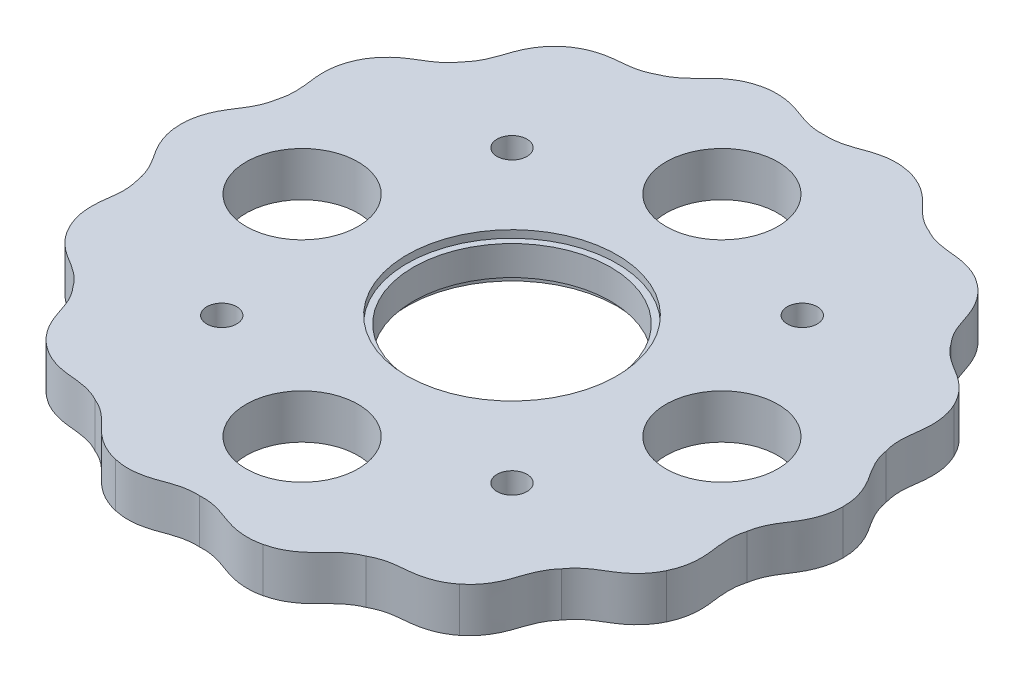
SolidWorks part; units mm, degrees
ref_plane "Front Plane" through (0, 0, 0) normal (0, 0, 1) x (1, 0, 0)
ref_plane "Top Plane" through (0, 0, 0) normal (0, 1, 0) x (1, 0, 0)
ref_plane "Right Plane" through (0, 0, 0) normal (1, 0, 0) x (0, 0, -1)
sketch "Sketch1" plane through (0, 0, 0) normal (0, 1, 0) x (1, 0, 0)
  line L0 (0, 0) -> (37.5, 0) construction
  line L1 (0, 0) -> (37.4807, 1.2019) construction
  line L2 (0, 0) -> (37.423, 2.4026) construction
  line L3 (0, 0) -> (37.3267, 3.6009) construction
  line L4 (0, 0) -> (37.1921, 4.7954) construction
  line L5 (0, 0) -> (37.0193, 5.985) construction
  line L6 (0, 0) -> (36.8085, 7.1684) construction
  line L7 (0, 0) -> (36.5598, 8.3445) construction
  line L8 (0, 0) -> (36.2736, 9.512) construction
  line L9 (0, 0) -> (35.95, 10.6698) construction
  line L10 (0, 0) -> (35.5896, 11.8166) construction
  line L11 (0, 0) -> (35.1926, 12.9512) construction
  line L12 (0, 0) -> (34.7594, 14.0725) construction
  line L13 (0, 0) -> (34.2905, 15.1794) construction
  line L14 (0, 0) -> (33.7863, 16.2706) construction
  line L15 (37.5, 0) -> (38.5, 0) construction
  line L16 (37.4807, 1.2019) -> (38.3521, 1.6927) construction
  line L17 (37.423, 2.4026) -> (37.9413, 3.2578) construction
  line L18 (37.3267, 3.6009) -> (37.3588, 4.6003) construction
  line L19 (37.1921, 4.7954) -> (36.7296, 5.682) construction
  line L20 (37.0193, 5.985) -> (36.1812, 6.5305) construction
  line L21 (36.8085, 7.1684) -> (35.8105, 7.2325) construction
  line L22 (36.5598, 8.3445) -> (35.5849, 8.122) construction
  line L23 (37, 0.0019) -> (37, 0)
  line L24 (33.3367, 16.052) -> (33.3358, 16.0537)
  line L25 (37, -0.0019) -> (37, 0)
  line L26 (33.3367, -16.052) -> (33.3358, -16.0537)
  line L27 (33.335, -16.0554) -> (33.3358, -16.0537)
  line L28 (23.0706, -28.9266) -> (23.0691, -28.9278)
  line L29 (23.0677, -28.9289) -> (23.0691, -28.9278)
  line L30 (8.2351, -36.0719) -> (8.2333, -36.0723)
  line L31 (8.2315, -36.0727) -> (8.2333, -36.0723)
  line L32 (-8.2315, -36.0727) -> (-8.2333, -36.0723)
  line L33 (-8.2351, -36.0719) -> (-8.2333, -36.0723)
  line L34 (-23.0677, -28.9289) -> (-23.0691, -28.9278)
  line L35 (-23.0706, -28.9266) -> (-23.0691, -28.9278)
  line L36 (-33.335, -16.0554) -> (-33.3358, -16.0537)
  line L37 (-33.3367, -16.052) -> (-33.3358, -16.0537)
  line L38 (-37, -0.0019) -> (-37, 0)
  line L39 (-37, 0.0019) -> (-37, 0)
  line L40 (-33.3367, 16.052) -> (-33.3358, 16.0537)
  line L41 (-33.335, 16.0554) -> (-33.3358, 16.0537)
  line L42 (-23.0706, 28.9266) -> (-23.0691, 28.9278)
  line L43 (-23.0677, 28.9289) -> (-23.0691, 28.9278)
  line L44 (-8.2351, 36.0719) -> (-8.2333, 36.0723)
  line L45 (-8.2315, 36.0727) -> (-8.2333, 36.0723)
  line L46 (8.2315, 36.0727) -> (8.2333, 36.0723)
  line L47 (8.2351, 36.0719) -> (8.2333, 36.0723)
  line L48 (23.0677, 28.9289) -> (23.0691, 28.9278)
  line L49 (23.0706, 28.9266) -> (23.0691, 28.9278)
  line L50 (33.335, 16.0554) -> (33.3358, 16.0537)
  line L51 (35.5, 0.0037) -> (35.5, 0)
  line L52 (31.986, 15.3995) -> (31.9844, 15.4029)
  line L53 (35.5, -0.0037) -> (35.5, 0)
  line L54 (31.986, -15.3995) -> (31.9844, -15.4029)
  line L55 (31.9828, -15.4062) -> (31.9844, -15.4029)
  line L56 (22.1368, -27.7527) -> (22.1339, -27.755)
  line L57 (22.131, -27.7573) -> (22.1339, -27.755)
  line L58 (7.9031, -34.6091) -> (7.8995, -34.6099)
  line L59 (7.8959, -34.6108) -> (7.8995, -34.6099)
  line L60 (-7.8959, -34.6108) -> (-7.8995, -34.6099)
  line L61 (-7.9031, -34.6091) -> (-7.8995, -34.6099)
  line L62 (-22.131, -27.7573) -> (-22.1339, -27.755)
  line L63 (-22.1368, -27.7527) -> (-22.1339, -27.755)
  line L64 (-31.9828, -15.4062) -> (-31.9844, -15.4029)
  line L65 (-31.986, -15.3995) -> (-31.9844, -15.4029)
  line L66 (-35.5, -0.0037) -> (-35.5, 0)
  line L67 (-35.5, 0.0037) -> (-35.5, 0)
  line L68 (-31.986, 15.3995) -> (-31.9844, 15.4029)
  line L69 (-31.9828, 15.4062) -> (-31.9844, 15.4029)
  line L70 (-22.1368, 27.7527) -> (-22.1339, 27.755)
  line L71 (-22.131, 27.7573) -> (-22.1339, 27.755)
  line L72 (-7.9031, 34.6091) -> (-7.8995, 34.6099)
  line L73 (-7.8959, 34.6108) -> (-7.8995, 34.6099)
  line L74 (7.8959, 34.6108) -> (7.8995, 34.6099)
  line L75 (7.9031, 34.6091) -> (7.8995, 34.6099)
  line L76 (22.131, 27.7573) -> (22.1339, 27.755)
  line L77 (22.1368, 27.7527) -> (22.1339, 27.755)
  line L78 (31.9828, 15.4062) -> (31.9844, 15.4029)
  circle A0 centre (0, 0) radius 35 construction
  circle A1 centre (37.5, 0) radius 2.5 construction
  circle A2 centre (0, 0) radius 37.5 construction
  spline S0 degree 3 poles (35.5849, 8.122) (35.6266, 7.5364) (36.0345, 6.7125) (36.7836, 5.6218) (37.4152, 4.5501) (38.2239, 2.702) (38.5014, 1.1074) (38.5, 0) knots 0 0 0 0 0.195516 0.310928 0.453873 0.621058 1 1 1 1
  spline S1 degree 3 poles (35.5849, 8.122) (35.3683, 8.6678) (35.3784, 9.5871) (35.5801, 10.8948) (35.6841, 12.1344) (35.611, 14.1503) (35.169, 15.7074) (34.6873, 16.7045) knots 0 0 0 0 0.195516 0.310928 0.453873 0.621058 1 1 1 1
  spline S2 degree 1 poles (34.1119, 7.7858) (33.3367, 16.052) knots 0 0 1 1 construction
  spline S3 degree 1 poles (34.1119, 7.7858) (37, 0.0019) knots 0 0 1 1 construction
  spline S4 degree 3 poles (33.3367, 16.052) (33.6005, 15.5058) (33.9037, 14.6401) (34.1146, 13.4372) (34.174, 12.5211) (34.1413, 11.5771) (34.0239, 10.6392) (33.8823, 9.6155) (33.9055, 8.625) (34.0243, 8.0514) (34.1119, 7.7858) knots 0.015853 0.015853 0.015853 0.015853 0.26189 0.384908 0.507927 0.630945 0.753963 0.876982 0.938491 1 1 1 1
  spline S5 degree 3 poles (34.1119, 7.7858) (34.1483, 7.5085) (34.2901, 6.9402) (34.6989, 6.0377) (35.2706, 5.1769) (35.7834, 4.3828) (36.2224, 3.5464) (36.5664, 2.6953) (36.8983, 1.52) (37.0008, 0.6085) (37, 0.0019) knots 0.015853 0.015853 0.015853 0.015853 0.077362 0.138872 0.26189 0.384908 0.507927 0.630945 0.753963 1 1 1 1
  spline S6 degree 3 poles (37, -0.0019) (37.0008, -0.6085) (36.8983, -1.52) (36.5664, -2.6953) (36.2224, -3.5464) (35.7834, -4.3828) (35.2706, -5.1769) (34.6989, -6.0377) (34.2901, -6.9402) (34.1483, -7.5085) (34.1119, -7.7858) knots 0.015853 0.015853 0.015853 0.015853 0.26189 0.384908 0.507927 0.630945 0.753963 0.876982 0.938491 1 1 1 1
  spline S7 degree 3 poles (34.1119, -7.7858) (34.0243, -8.0514) (33.9055, -8.625) (33.8823, -9.6155) (34.0239, -10.6392) (34.1413, -11.5771) (34.174, -12.5211) (34.1146, -13.4372) (33.9037, -14.6401) (33.6005, -15.5058) (33.3367, -16.052) knots 0.015853 0.015853 0.015853 0.015853 0.077362 0.138872 0.26189 0.384908 0.507927 0.630945 0.753963 1 1 1 1
  spline S8 degree 3 poles (33.335, -16.0554) (33.0725, -16.6022) (32.5847, -17.3791) (31.7758, -18.2939) (31.0965, -18.9115) (30.3381, -19.4746) (29.5316, -19.9675) (28.6429, -20.4951) (27.8831, -21.1308) (27.5087, -21.5813) (27.3556, -21.8154) knots 0.015853 0.015853 0.015853 0.015853 0.26189 0.384908 0.507927 0.630945 0.753963 0.876982 0.938491 1 1 1 1
  spline S9 degree 3 poles (27.3556, -21.8154) (27.1615, -22.0167) (26.8056, -22.4819) (26.3549, -23.3642) (26.0383, -24.348) (25.7371, -25.2439) (25.357, -26.1087) (24.906, -26.9083) (24.1941, -27.9005) (23.5453, -28.549) (23.0706, -28.9266) knots 0.015853 0.015853 0.015853 0.015853 0.077362 0.138872 0.26189 0.384908 0.507927 0.630945 0.753963 1 1 1 1
  spline S10 degree 3 poles (23.0677, -28.9289) (22.5939, -29.3077) (21.8173, -29.796) (20.6915, -30.2693) (19.8116, -30.531) (18.884, -30.7092) (17.9435, -30.8034) (16.9139, -30.8931) (15.9535, -31.1362) (15.4207, -31.3797) (15.1812, -31.5241) knots 0.015853 0.015853 0.015853 0.015853 0.26189 0.384908 0.507927 0.630945 0.753963 0.876982 0.938491 1 1 1 1
  spline S11 degree 3 poles (15.1812, -31.5241) (14.919, -31.6213) (14.3964, -31.886) (13.6076, -32.4854) (12.8955, -33.2344) (12.2354, -33.9109) (11.5177, -34.5251) (10.7645, -35.0499) (9.6926, -35.6349) (8.8266, -35.9377) (8.2351, -36.0719) knots 0.015853 0.015853 0.015853 0.015853 0.077362 0.138872 0.26189 0.384908 0.507927 0.630945 0.753963 1 1 1 1
  spline S12 degree 3 poles (8.2315, -36.0727) (7.6402, -36.2085) (6.7287, -36.3114) (5.5091, -36.2494) (4.6028, -36.1034) (3.6897, -35.8614) (2.8014, -35.5383) (1.8349, -35.1724) (0.8641, -34.9747) (0.2785, -34.9629) (0, -34.9891) knots 0.015853 0.015853 0.015853 0.015853 0.26189 0.384908 0.507927 0.630945 0.753963 0.876982 0.938491 1 1 1 1
  spline S13 degree 3 poles (0, -34.9891) (-0.2785, -34.9629) (-0.8641, -34.9747) (-1.8349, -35.1724) (-2.8014, -35.5383) (-3.6897, -35.8614) (-4.6028, -36.1034) (-5.5091, -36.2494) (-6.7287, -36.3114) (-7.6402, -36.2085) (-8.2315, -36.0727) knots 0.015853 0.015853 0.015853 0.015853 0.077362 0.138872 0.26189 0.384908 0.507927 0.630945 0.753963 1 1 1 1
  spline S14 degree 3 poles (-8.2351, -36.0719) (-8.8266, -35.9377) (-9.6926, -35.6349) (-10.7645, -35.0499) (-11.5177, -34.5251) (-12.2354, -33.9109) (-12.8955, -33.2344) (-13.6076, -32.4854) (-14.3964, -31.886) (-14.919, -31.6213) (-15.1812, -31.5241) knots 0.015853 0.015853 0.015853 0.015853 0.26189 0.384908 0.507927 0.630945 0.753963 0.876982 0.938491 1 1 1 1
  spline S15 degree 3 poles (-15.1812, -31.5241) (-15.4207, -31.3797) (-15.9535, -31.1362) (-16.9139, -30.8931) (-17.9435, -30.8034) (-18.884, -30.7092) (-19.8116, -30.531) (-20.6915, -30.2693) (-21.8173, -29.796) (-22.5939, -29.3077) (-23.0677, -28.9289) knots 0.015853 0.015853 0.015853 0.015853 0.077362 0.138872 0.26189 0.384908 0.507927 0.630945 0.753963 1 1 1 1
  spline S16 degree 3 poles (-23.0706, -28.9266) (-23.5453, -28.549) (-24.1941, -27.9005) (-24.906, -26.9083) (-25.357, -26.1087) (-25.7371, -25.2439) (-26.0383, -24.348) (-26.3549, -23.3642) (-26.8056, -22.4819) (-27.1615, -22.0167) (-27.3556, -21.8154) knots 0.015853 0.015853 0.015853 0.015853 0.26189 0.384908 0.507927 0.630945 0.753963 0.876982 0.938491 1 1 1 1
  spline S17 degree 3 poles (-27.3556, -21.8154) (-27.5087, -21.5813) (-27.8831, -21.1308) (-28.6429, -20.4951) (-29.5316, -19.9675) (-30.3381, -19.4746) (-31.0965, -18.9115) (-31.7758, -18.2939) (-32.5847, -17.3791) (-33.0725, -16.6022) (-33.335, -16.0554) knots 0.015853 0.015853 0.015853 0.015853 0.077362 0.138872 0.26189 0.384908 0.507927 0.630945 0.753963 1 1 1 1
  spline S18 degree 3 poles (-33.3367, -16.052) (-33.6005, -15.5058) (-33.9037, -14.6401) (-34.1146, -13.4372) (-34.174, -12.5211) (-34.1413, -11.5771) (-34.0239, -10.6392) (-33.8823, -9.6155) (-33.9055, -8.625) (-34.0243, -8.0514) (-34.1119, -7.7858) knots 0.015853 0.015853 0.015853 0.015853 0.26189 0.384908 0.507927 0.630945 0.753963 0.876982 0.938491 1 1 1 1
  spline S19 degree 3 poles (-34.1119, -7.7858) (-34.1483, -7.5085) (-34.2901, -6.9402) (-34.6989, -6.0377) (-35.2706, -5.1769) (-35.7834, -4.3828) (-36.2224, -3.5464) (-36.5664, -2.6953) (-36.8983, -1.52) (-37.0008, -0.6085) (-37, -0.0019) knots 0.015853 0.015853 0.015853 0.015853 0.077362 0.138872 0.26189 0.384908 0.507927 0.630945 0.753963 1 1 1 1
  spline S20 degree 3 poles (-37, 0.0019) (-37.0008, 0.6085) (-36.8983, 1.52) (-36.5664, 2.6953) (-36.2224, 3.5464) (-35.7834, 4.3828) (-35.2706, 5.1769) (-34.6989, 6.0377) (-34.2901, 6.9402) (-34.1483, 7.5085) (-34.1119, 7.7858) knots 0.015853 0.015853 0.015853 0.015853 0.26189 0.384908 0.507927 0.630945 0.753963 0.876982 0.938491 1 1 1 1
  spline S21 degree 3 poles (-34.1119, 7.7858) (-34.0243, 8.0514) (-33.9055, 8.625) (-33.8823, 9.6155) (-34.0239, 10.6392) (-34.1413, 11.5771) (-34.174, 12.5211) (-34.1146, 13.4372) (-33.9037, 14.6401) (-33.6005, 15.5058) (-33.3367, 16.052) knots 0.015853 0.015853 0.015853 0.015853 0.077362 0.138872 0.26189 0.384908 0.507927 0.630945 0.753963 1 1 1 1
  spline S22 degree 3 poles (-33.335, 16.0554) (-33.0725, 16.6022) (-32.5847, 17.3791) (-31.7758, 18.2939) (-31.0965, 18.9115) (-30.3381, 19.4746) (-29.5316, 19.9675) (-28.6429, 20.4951) (-27.8831, 21.1308) (-27.5087, 21.5813) (-27.3556, 21.8154) knots 0.015853 0.015853 0.015853 0.015853 0.26189 0.384908 0.507927 0.630945 0.753963 0.876982 0.938491 1 1 1 1
  spline S23 degree 3 poles (-27.3556, 21.8154) (-27.1615, 22.0167) (-26.8056, 22.4819) (-26.3549, 23.3642) (-26.0383, 24.348) (-25.7371, 25.2439) (-25.357, 26.1087) (-24.906, 26.9083) (-24.1941, 27.9005) (-23.5453, 28.549) (-23.0706, 28.9266) knots 0.015853 0.015853 0.015853 0.015853 0.077362 0.138872 0.26189 0.384908 0.507927 0.630945 0.753963 1 1 1 1
  spline S24 degree 3 poles (-23.0677, 28.9289) (-22.5939, 29.3077) (-21.8173, 29.796) (-20.6915, 30.2693) (-19.8116, 30.531) (-18.884, 30.7092) (-17.9435, 30.8034) (-16.9139, 30.8931) (-15.9535, 31.1362) (-15.4207, 31.3797) (-15.1812, 31.5241) knots 0.015853 0.015853 0.015853 0.015853 0.26189 0.384908 0.507927 0.630945 0.753963 0.876982 0.938491 1 1 1 1
  spline S25 degree 3 poles (-15.1812, 31.5241) (-14.919, 31.6213) (-14.3964, 31.886) (-13.6076, 32.4854) (-12.8955, 33.2344) (-12.2354, 33.9109) (-11.5177, 34.5251) (-10.7645, 35.0499) (-9.6926, 35.6349) (-8.8266, 35.9377) (-8.2351, 36.0719) knots 0.015853 0.015853 0.015853 0.015853 0.077362 0.138872 0.26189 0.384908 0.507927 0.630945 0.753963 1 1 1 1
  spline S26 degree 3 poles (-8.2315, 36.0727) (-7.6402, 36.2085) (-6.7287, 36.3114) (-5.5091, 36.2494) (-4.6028, 36.1034) (-3.6897, 35.8614) (-2.8014, 35.5383) (-1.8349, 35.1724) (-0.8641, 34.9747) (-0.2785, 34.9629) (0, 34.9891) knots 0.015853 0.015853 0.015853 0.015853 0.26189 0.384908 0.507927 0.630945 0.753963 0.876982 0.938491 1 1 1 1
  spline S27 degree 3 poles (0, 34.9891) (0.2785, 34.9629) (0.8641, 34.9747) (1.8349, 35.1724) (2.8014, 35.5383) (3.6897, 35.8614) (4.6028, 36.1034) (5.5091, 36.2494) (6.7287, 36.3114) (7.6402, 36.2085) (8.2315, 36.0727) knots 0.015853 0.015853 0.015853 0.015853 0.077362 0.138872 0.26189 0.384908 0.507927 0.630945 0.753963 1 1 1 1
  spline S28 degree 3 poles (8.2351, 36.0719) (8.8266, 35.9377) (9.6926, 35.6349) (10.7645, 35.0499) (11.5177, 34.5251) (12.2354, 33.9109) (12.8955, 33.2344) (13.6076, 32.4854) (14.3964, 31.886) (14.919, 31.6213) (15.1812, 31.5241) knots 0.015853 0.015853 0.015853 0.015853 0.26189 0.384908 0.507927 0.630945 0.753963 0.876982 0.938491 1 1 1 1
  spline S29 degree 3 poles (15.1812, 31.5241) (15.4207, 31.3797) (15.9535, 31.1362) (16.9139, 30.8931) (17.9435, 30.8034) (18.884, 30.7092) (19.8116, 30.531) (20.6915, 30.2693) (21.8173, 29.796) (22.5939, 29.3077) (23.0677, 28.9289) knots 0.015853 0.015853 0.015853 0.015853 0.077362 0.138872 0.26189 0.384908 0.507927 0.630945 0.753963 1 1 1 1
  spline S30 degree 3 poles (23.0706, 28.9266) (23.5453, 28.549) (24.1941, 27.9005) (24.906, 26.9083) (25.357, 26.1087) (25.7371, 25.2439) (26.0383, 24.348) (26.3549, 23.3642) (26.8056, 22.4819) (27.1615, 22.0167) (27.3556, 21.8154) knots 0.015853 0.015853 0.015853 0.015853 0.26189 0.384908 0.507927 0.630945 0.753963 0.876982 0.938491 1 1 1 1
  spline S31 degree 3 poles (27.3556, 21.8154) (27.5087, 21.5813) (27.8831, 21.1308) (28.6429, 20.4951) (29.5316, 19.9675) (30.3381, 19.4746) (31.0965, 18.9115) (31.7758, 18.2939) (32.5847, 17.3791) (33.0725, 16.6022) (33.335, 16.0554) knots 0.015853 0.015853 0.015853 0.015853 0.077362 0.138872 0.26189 0.384908 0.507927 0.630945 0.753963 1 1 1 1
  spline S32 degree 1 poles (32.6448, 7.451) (35.5, 0.0037) knots 0 0 1 1 construction
  spline S33 degree 1 poles (32.6448, 7.451) (31.986, 15.3995) knots 0 0 1 1 construction
  spline S34 degree 3 poles (35.5, 0.0037) (35.5006, 0.4959) (35.4183, 1.2336) (35.1496, 2.1927) (34.8707, 2.8896) (34.4997, 3.6015) (34.1394, 4.1652) (33.6939, 4.8394) (33.3068, 5.4873) (32.9751, 6.1975) (32.758, 6.8733) (32.6748, 7.2607) (32.6448, 7.451) knots 0.023011 0.023011 0.023011 0.023011 0.267258 0.389382 0.511505 0.633629 0.755753 0.816814 0.877876 0.938938 0.969469 1 1 1 1
  spline S35 degree 3 poles (32.6448, 7.451) (32.5893, 7.6354) (32.4961, 8.0206) (32.3985, 8.7236) (32.3893, 9.5074) (32.4569, 10.2591) (32.5657, 11.0598) (32.6458, 11.724) (32.6712, 12.5264) (32.6201, 13.2752) (32.446, 14.256) (32.2001, 14.9563) (31.986, 15.3995) knots 0.023011 0.023011 0.023011 0.023011 0.053542 0.084072 0.145134 0.206196 0.267258 0.389382 0.511505 0.633629 0.755753 1 1 1 1
  spline S36 degree 3 poles (32.6448, -7.451) (32.6748, -7.2607) (32.758, -6.8733) (32.9751, -6.1975) (33.3068, -5.4873) (33.6939, -4.8394) (34.1394, -4.1652) (34.4997, -3.6015) (34.8707, -2.8896) (35.1496, -2.1927) (35.4183, -1.2336) (35.5006, -0.4959) (35.5, -0.0037) knots 0.023011 0.023011 0.023011 0.023011 0.053542 0.084072 0.145134 0.206196 0.267258 0.389382 0.511505 0.633629 0.755753 1 1 1 1
  spline S37 degree 3 poles (31.986, -15.3995) (32.2001, -14.9563) (32.446, -14.256) (32.6201, -13.2752) (32.6712, -12.5264) (32.6458, -11.724) (32.5657, -11.0598) (32.4569, -10.2591) (32.3893, -9.5074) (32.3985, -8.7236) (32.4961, -8.0206) (32.5893, -7.6354) (32.6448, -7.451) knots 0.023011 0.023011 0.023011 0.023011 0.267258 0.389382 0.511505 0.633629 0.755753 0.816814 0.877876 0.938938 0.969469 1 1 1 1
  spline S38 degree 3 poles (26.1791, -20.8771) (26.2887, -20.7187) (26.5317, -20.4057) (27.0205, -19.8911) (27.6275, -19.3952) (28.2574, -18.9793) (28.9513, -18.5652) (29.5206, -18.2137) (30.1637, -17.7333) (30.7173, -17.2264) (31.3755, -16.4789) (31.7698, -15.8499) (31.9828, -15.4062) knots 0.023011 0.023011 0.023011 0.023011 0.053542 0.084072 0.145134 0.206196 0.267258 0.389382 0.511505 0.633629 0.755753 1 1 1 1
  spline S39 degree 3 poles (22.1368, -27.7527) (22.522, -27.4463) (23.0474, -26.922) (23.6297, -26.1139) (24.0007, -25.4614) (24.326, -24.7275) (24.542, -24.0943) (24.7914, -23.3257) (25.0566, -22.619) (25.405, -21.9169) (25.798, -21.3258) (26.0491, -21.0192) (26.1791, -20.8771) knots 0.023011 0.023011 0.023011 0.023011 0.267258 0.389382 0.511505 0.633629 0.755753 0.816814 0.877876 0.938938 0.969469 1 1 1 1
  spline S40 degree 3 poles (14.5283, -30.1683) (14.6957, -30.0732) (15.0505, -29.8966) (15.7143, -29.645) (16.4763, -29.4616) (17.2242, -29.3602) (18.0291, -29.2882) (18.6945, -29.2185) (19.4823, -29.0647) (20.201, -28.8482) (21.1184, -28.4603) (21.7465, -28.0647) (22.131, -27.7573) knots 0.023011 0.023011 0.023011 0.023011 0.053542 0.084072 0.145134 0.206196 0.267258 0.389382 0.511505 0.633629 0.755753 1 1 1 1
  spline S41 degree 3 poles (7.9031, -34.6091) (8.3831, -34.5002) (9.084, -34.2557) (9.9593, -33.7804) (10.5766, -33.3534) (11.1881, -32.8334) (11.6575, -32.3566) (12.2156, -31.7723) (12.7612, -31.2507) (13.3797, -30.7693) (13.9903, -30.4072) (14.3495, -30.2399) (14.5283, -30.1683) knots 0.023011 0.023011 0.023011 0.023011 0.267258 0.389382 0.511505 0.633629 0.755753 0.816814 0.877876 0.938938 0.969469 1 1 1 1
  spline S42 degree 3 poles (0, -33.4843) (0.1922, -33.4712) (0.5884, -33.4661) (1.2956, -33.5274) (2.0617, -33.6928) (2.7796, -33.926) (3.536, -34.2103) (4.1657, -34.4362) (4.9423, -34.6394) (5.6838, -34.7562) (6.6786, -34.8048) (7.4161, -34.7209) (7.8959, -34.6108) knots 0.023011 0.023011 0.023011 0.023011 0.053542 0.084072 0.145134 0.206196 0.267258 0.389382 0.511505 0.633629 0.755753 1 1 1 1
  spline S43 degree 3 poles (-7.8959, -34.6108) (-7.4161, -34.7209) (-6.6786, -34.8048) (-5.6838, -34.7562) (-4.9423, -34.6394) (-4.1657, -34.4362) (-3.536, -34.2103) (-2.7796, -33.926) (-2.0617, -33.6928) (-1.2956, -33.5274) (-0.5884, -33.4661) (-0.1922, -33.4712) (0, -33.4843) knots 0.023011 0.023011 0.023011 0.023011 0.267258 0.389382 0.511505 0.633629 0.755753 0.816814 0.877876 0.938938 0.969469 1 1 1 1
  spline S44 degree 3 poles (-14.5283, -30.1683) (-14.3495, -30.2399) (-13.9903, -30.4072) (-13.3797, -30.7693) (-12.7612, -31.2507) (-12.2156, -31.7723) (-11.6575, -32.3566) (-11.1881, -32.8334) (-10.5766, -33.3534) (-9.9593, -33.7804) (-9.084, -34.2557) (-8.3831, -34.5002) (-7.9031, -34.6091) knots 0.023011 0.023011 0.023011 0.023011 0.053542 0.084072 0.145134 0.206196 0.267258 0.389382 0.511505 0.633629 0.755753 1 1 1 1
  spline S45 degree 3 poles (-22.131, -27.7573) (-21.7465, -28.0647) (-21.1184, -28.4603) (-20.201, -28.8482) (-19.4823, -29.0647) (-18.6945, -29.2185) (-18.0291, -29.2882) (-17.2242, -29.3602) (-16.4763, -29.4616) (-15.7143, -29.645) (-15.0505, -29.8966) (-14.6957, -30.0732) (-14.5283, -30.1683) knots 0.023011 0.023011 0.023011 0.023011 0.267258 0.389382 0.511505 0.633629 0.755753 0.816814 0.877876 0.938938 0.969469 1 1 1 1
  spline S46 degree 3 poles (-26.1791, -20.8771) (-26.0491, -21.0192) (-25.798, -21.3258) (-25.405, -21.9169) (-25.0566, -22.619) (-24.7914, -23.3257) (-24.542, -24.0943) (-24.326, -24.7275) (-24.0007, -25.4614) (-23.6297, -26.1139) (-23.0474, -26.922) (-22.522, -27.4463) (-22.1368, -27.7527) knots 0.023011 0.023011 0.023011 0.023011 0.053542 0.084072 0.145134 0.206196 0.267258 0.389382 0.511505 0.633629 0.755753 1 1 1 1
  spline S47 degree 3 poles (-31.9828, -15.4062) (-31.7698, -15.8499) (-31.3755, -16.4789) (-30.7173, -17.2264) (-30.1637, -17.7333) (-29.5206, -18.2137) (-28.9513, -18.5652) (-28.2574, -18.9793) (-27.6275, -19.3952) (-27.0205, -19.8911) (-26.5317, -20.4057) (-26.2887, -20.7187) (-26.1791, -20.8771) knots 0.023011 0.023011 0.023011 0.023011 0.267258 0.389382 0.511505 0.633629 0.755753 0.816814 0.877876 0.938938 0.969469 1 1 1 1
  spline S48 degree 3 poles (-32.6448, -7.451) (-32.5893, -7.6354) (-32.4961, -8.0206) (-32.3985, -8.7236) (-32.3893, -9.5074) (-32.4569, -10.2591) (-32.5657, -11.0598) (-32.6458, -11.724) (-32.6712, -12.5264) (-32.6201, -13.2752) (-32.446, -14.256) (-32.2001, -14.9563) (-31.986, -15.3995) knots 0.023011 0.023011 0.023011 0.023011 0.053542 0.084072 0.145134 0.206196 0.267258 0.389382 0.511505 0.633629 0.755753 1 1 1 1
  spline S49 degree 3 poles (-35.5, -0.0037) (-35.5006, -0.4959) (-35.4183, -1.2336) (-35.1496, -2.1927) (-34.8707, -2.8896) (-34.4997, -3.6015) (-34.1394, -4.1652) (-33.6939, -4.8394) (-33.3068, -5.4873) (-32.9751, -6.1975) (-32.758, -6.8733) (-32.6748, -7.2607) (-32.6448, -7.451) knots 0.023011 0.023011 0.023011 0.023011 0.267258 0.389382 0.511505 0.633629 0.755753 0.816814 0.877876 0.938938 0.969469 1 1 1 1
  spline S50 degree 3 poles (-32.6448, 7.451) (-32.6748, 7.2607) (-32.758, 6.8733) (-32.9751, 6.1975) (-33.3068, 5.4873) (-33.6939, 4.8394) (-34.1394, 4.1652) (-34.4997, 3.6015) (-34.8707, 2.8896) (-35.1496, 2.1927) (-35.4183, 1.2336) (-35.5006, 0.4959) (-35.5, 0.0037) knots 0.023011 0.023011 0.023011 0.023011 0.053542 0.084072 0.145134 0.206196 0.267258 0.389382 0.511505 0.633629 0.755753 1 1 1 1
  spline S51 degree 3 poles (-31.986, 15.3995) (-32.2001, 14.9563) (-32.446, 14.256) (-32.6201, 13.2752) (-32.6712, 12.5264) (-32.6458, 11.724) (-32.5657, 11.0598) (-32.4569, 10.2591) (-32.3893, 9.5074) (-32.3985, 8.7236) (-32.4961, 8.0206) (-32.5893, 7.6354) (-32.6448, 7.451) knots 0.023011 0.023011 0.023011 0.023011 0.267258 0.389382 0.511505 0.633629 0.755753 0.816814 0.877876 0.938938 0.969469 1 1 1 1
  spline S52 degree 3 poles (-26.1791, 20.8771) (-26.2887, 20.7187) (-26.5317, 20.4057) (-27.0205, 19.8911) (-27.6275, 19.3952) (-28.2574, 18.9793) (-28.9513, 18.5652) (-29.5206, 18.2137) (-30.1637, 17.7333) (-30.7173, 17.2264) (-31.3755, 16.4789) (-31.7698, 15.8499) (-31.9828, 15.4062) knots 0.023011 0.023011 0.023011 0.023011 0.053542 0.084072 0.145134 0.206196 0.267258 0.389382 0.511505 0.633629 0.755753 1 1 1 1
  spline S53 degree 3 poles (-22.1368, 27.7527) (-22.522, 27.4463) (-23.0474, 26.922) (-23.6297, 26.1139) (-24.0007, 25.4614) (-24.326, 24.7275) (-24.542, 24.0943) (-24.7914, 23.3257) (-25.0566, 22.619) (-25.405, 21.9169) (-25.798, 21.3258) (-26.0491, 21.0192) (-26.1791, 20.8771) knots 0.023011 0.023011 0.023011 0.023011 0.267258 0.389382 0.511505 0.633629 0.755753 0.816814 0.877876 0.938938 0.969469 1 1 1 1
  spline S54 degree 3 poles (-14.5283, 30.1683) (-14.6957, 30.0732) (-15.0505, 29.8966) (-15.7143, 29.645) (-16.4763, 29.4616) (-17.2242, 29.3602) (-18.0291, 29.2882) (-18.6945, 29.2185) (-19.4823, 29.0647) (-20.201, 28.8482) (-21.1184, 28.4603) (-21.7465, 28.0647) (-22.131, 27.7573) knots 0.023011 0.023011 0.023011 0.023011 0.053542 0.084072 0.145134 0.206196 0.267258 0.389382 0.511505 0.633629 0.755753 1 1 1 1
  spline S55 degree 3 poles (-7.9031, 34.6091) (-8.3831, 34.5002) (-9.084, 34.2557) (-9.9593, 33.7804) (-10.5766, 33.3534) (-11.1881, 32.8334) (-11.6575, 32.3566) (-12.2156, 31.7723) (-12.7612, 31.2507) (-13.3797, 30.7693) (-13.9903, 30.4072) (-14.3495, 30.2399) (-14.5283, 30.1683) knots 0.023011 0.023011 0.023011 0.023011 0.267258 0.389382 0.511505 0.633629 0.755753 0.816814 0.877876 0.938938 0.969469 1 1 1 1
  spline S56 degree 3 poles (0, 33.4843) (-0.1922, 33.4712) (-0.5884, 33.4661) (-1.2956, 33.5274) (-2.0617, 33.6928) (-2.7796, 33.926) (-3.536, 34.2103) (-4.1657, 34.4362) (-4.9423, 34.6394) (-5.6838, 34.7562) (-6.6786, 34.8048) (-7.4161, 34.7209) (-7.8959, 34.6108) knots 0.023011 0.023011 0.023011 0.023011 0.053542 0.084072 0.145134 0.206196 0.267258 0.389382 0.511505 0.633629 0.755753 1 1 1 1
  spline S57 degree 3 poles (7.8959, 34.6108) (7.4161, 34.7209) (6.6786, 34.8048) (5.6838, 34.7562) (4.9423, 34.6394) (4.1657, 34.4362) (3.536, 34.2103) (2.7796, 33.926) (2.0617, 33.6928) (1.2956, 33.5274) (0.5884, 33.4661) (0.1922, 33.4712) (0, 33.4843) knots 0.023011 0.023011 0.023011 0.023011 0.267258 0.389382 0.511505 0.633629 0.755753 0.816814 0.877876 0.938938 0.969469 1 1 1 1
  spline S58 degree 3 poles (14.5283, 30.1683) (14.3495, 30.2399) (13.9903, 30.4072) (13.3797, 30.7693) (12.7612, 31.2507) (12.2156, 31.7723) (11.6575, 32.3566) (11.1881, 32.8334) (10.5766, 33.3534) (9.9593, 33.7804) (9.084, 34.2557) (8.3831, 34.5002) (7.9031, 34.6091) knots 0.023011 0.023011 0.023011 0.023011 0.053542 0.084072 0.145134 0.206196 0.267258 0.389382 0.511505 0.633629 0.755753 1 1 1 1
  spline S59 degree 3 poles (22.131, 27.7573) (21.7465, 28.0647) (21.1184, 28.4603) (20.201, 28.8482) (19.4823, 29.0647) (18.6945, 29.2185) (18.0291, 29.2882) (17.2242, 29.3602) (16.4763, 29.4616) (15.7143, 29.645) (15.0505, 29.8966) (14.6957, 30.0732) (14.5283, 30.1683) knots 0.023011 0.023011 0.023011 0.023011 0.267258 0.389382 0.511505 0.633629 0.755753 0.816814 0.877876 0.938938 0.969469 1 1 1 1
  spline S60 degree 3 poles (26.1791, 20.8771) (26.0491, 21.0192) (25.798, 21.3258) (25.405, 21.9169) (25.0566, 22.619) (24.7914, 23.3257) (24.542, 24.0943) (24.326, 24.7275) (24.0007, 25.4614) (23.6297, 26.1139) (23.0474, 26.922) (22.522, 27.4463) (22.1368, 27.7527) knots 0.023011 0.023011 0.023011 0.023011 0.053542 0.084072 0.145134 0.206196 0.267258 0.389382 0.511505 0.633629 0.755753 1 1 1 1
  spline S61 degree 3 poles (31.9828, 15.4062) (31.7698, 15.8499) (31.3755, 16.4789) (30.7173, 17.2264) (30.1637, 17.7333) (29.5206, 18.2137) (28.9513, 18.5652) (28.2574, 18.9793) (27.6275, 19.3952) (27.0205, 19.8911) (26.5317, 20.4057) (26.2887, 20.7187) (26.1791, 20.8771) knots 0.023011 0.023011 0.023011 0.023011 0.267258 0.389382 0.511505 0.633629 0.755753 0.816814 0.877876 0.938938 0.969469 1 1 1 1
  point P25 (0, 0)
  point P117 (0, 0)
  point P174 (0, 0)
  dimension "D1" = 70
  dimension "D2" = 5
  dimension "D4" = 25.714
  dimension "D5" = 1
  dimension "D7" = 180
  dimension "D8" = 207.551
  dimension "D6" = 1
  dimension "D9" = 1
  dimension "D10" = 235.102
  dimension "D11" = 1
  dimension "D12" = 1
  dimension "D13" = 1
  dimension "D14" = 1
  dimension "D15" = 1
  dimension "D16" = 262.653
  dimension "D17" = 290.204
  dimension "D18" = 317.755
  dimension "D19" = 345.306
  dimension "D20" = 1.5
  dimension "D22" = 3
  dimension "D3" = 15
  dimension "D21" = 14
  dimension "D23" = 14
extrude "Boss-Extrude3" add sketch "Sketch1" along normal blind 4.7625 contours L51 L53 S36 S37 L54 L55 S38 S39 L56 L57 S40 S41 L58 L59 S42 S43 L60 L61 S44 S45 L62 L63 S46 S47 L64 L65 S48 S49 L66 L67 S50 S51 L68 L69 S52 S53 L70 L71 S54 S55 L72 L73 S56 S57 L74 L75 S58 S59 L76 L77 S60 S61 L78 L52 S35 S34
sketch "Sketch2" plane through (0, 4.7625, 0) normal (0, 1, 0) x (1, 0, 0)
  line L0 (0, 0) -> (22.5, 0) construction
  line L1 (0, 0) -> (15.5563, 15.5563) construction
  circle A0 centre (0, 0) radius 10.5635
  circle A1 centre (22.5, 0) radius 6
  circle A6 centre (15.5563, 15.5563) radius 1.607
  circle A7 centre (0, -22.5) radius 6
  circle A8 centre (15.5563, -15.5563) radius 1.607
  circle A9 centre (-22.5, 0) radius 6
  circle A10 centre (-15.5563, -15.5563) radius 1.607
  circle A11 centre (0, 22.5) radius 6
  circle A12 centre (-15.5563, 15.5563) radius 1.607
  point P16 (0, 0)
  point P21 (0, 0)
  point P24 (0, 0)
  dimension "D3" = 12
  dimension "D1" = 21.127
  dimension "D6" = 3.214
  dimension "D2" = 22.5
  dimension "D4" = 45
  dimension "D5" = 22
  dimension "D7" = 4
extrude "Cut-Extrude1" cut sketch "Sketch2" against normal blind 4.7625 contours A7 | A0 | A0 | A0 | L0 A0 | A0 L0 | A1 | A9 | A11 region at (0, 4.7625, 0) region at (22.5, 4.7625, 0) region at (0, 4.7625, 22.5) region at (-22.5, 4.7625, 0) region at (0, 4.7625, -22.5)
extrude "Cut-Extrude2" cut sketch "Sketch2<4>" against normal blind 2.4105 contours A12 | A10 | A8 | A6 region at (15.5563, 4.7625, -15.5563) region at (15.5563, 4.7625, 15.5563) region at (-15.5563, 4.7625, 15.5563) region at (-15.5563, 4.7625, -15.5563)
sketch "Sketch2<4>" plane through (0, 4.7625, 0) normal (0, 1, 0) x (1, 0, 0) same geometry as "Sketch2"
sketch "Sketch3" plane through (0, 4.7625, 0) normal (0, 1, 0) x (1, 0, 0)
  circle A0 centre (0, 0) radius 11.25
  dimension "D1" = 22.5
extrude "Cut-Extrude3" cut sketch "Sketch3" against normal blind 0.8
extrude "Cut-Extrude4" cut sketch "Sketch3<2>" along normal blind 0.8 from surface starting at face at (0, 0, 28.5)
sketch "Sketch3<2>" plane through (0, 4.7625, 0) normal (0, 1, 0) x (1, 0, 0) same geometry as "Sketch3"
equation "\"D5@Sketch1\" = \"eccentricity\""
equation "\"D6@Sketch1\" = \"eccentricity\""
equation "\"D9@Sketch1\" = \"eccentricity\""
equation "\"D11@Sketch1\" = \"eccentricity\""
equation "\"D12@Sketch1\" = \"eccentricity\""
equation "\"D14@Sketch1\" = \"eccentricity\""
equation "\"D13@Sketch1\" = \"eccentricity\""
equation "\"D15@Sketch1\"= \"eccentricity\""
equation "\"D1@Sketch2\"=\"largeBearOD\"+\"largeBearOTight\""
equation "\"D1@Cut-Extrude2\"=\"ballBearDiam\" * 0.75"
equation "\"D1@Boss-Extrude3\"=\"sheetThickness\""
equation "\"smallBearOD\"= 15mm"
equation "\"smallBearID\" = 10mm"
equation "\"smallBearOTight\"= 0mm'calibrate - hold onto bottom of gearbox"
equation "\"smallBearOLoose\"= 0mm'calibrate - able to take off topHat"
equation "\"smallBearITight\" = 0mm'hold onto "
equation "\"pinCircleDiam\"= 75mm"
equation "\"pinDiam\"= 6mm"
equation "\"sheetThickness\"= 0.1875in"
equation "\"D6@Sketch2\"=\"ballBearDiam\""
equation "\"largeBearOD\"= 21mm"
equation "\"largeBearID\" = 15mm"
equation "\"largeBearOTight\"= 0.127mm'calibrate - hold onto gears"
equation "\"largeBearITight\"= 0mm'calibrate - hold onto eccentric nut"
equation "\"ballBearDiam\"= 3.214mm"
equation "\"thrustBearingThickness\"= 5mm'measure this irl and change"
equation "\"thrustBearingID\"= 0mm'measure this irl and change"
equation "\"thrustBearingOD\"= 0mm'measure this irl and change"
equation "\"eccentricity\" = 1mm"
equation "\"D1@Cut-Extrude1\"=\"sheetThickness\""
